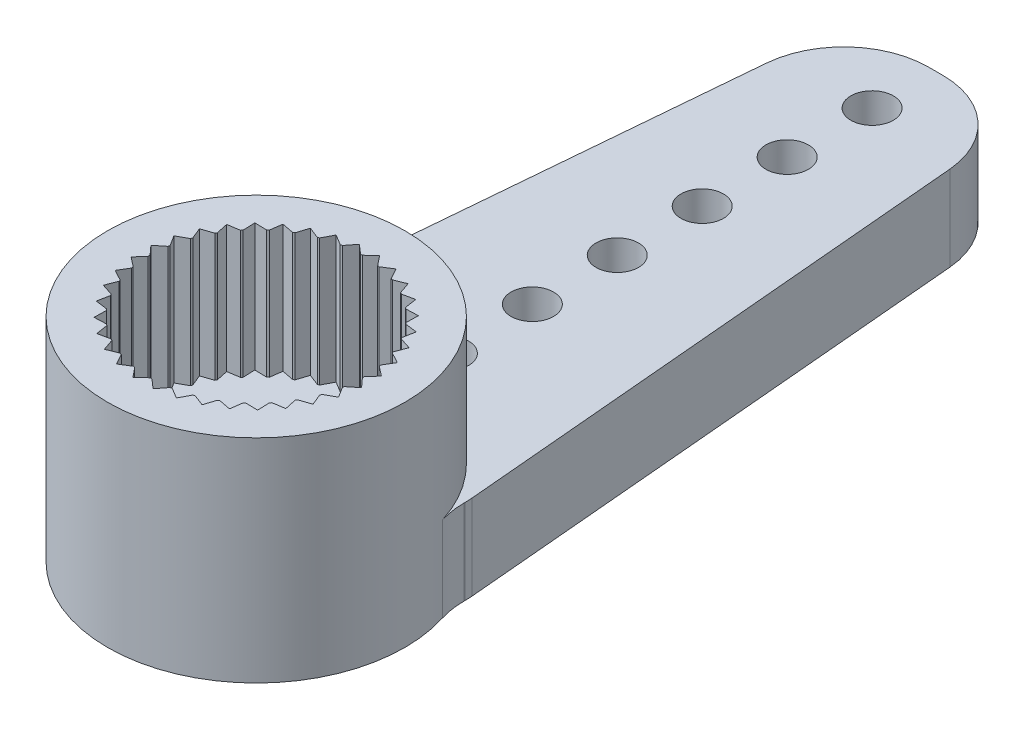
SolidWorks part; units mm, degrees
ref_plane "Front Plane" through (0, 0, 0) normal (0, 0, 1) x (1, 0, 0)
ref_plane "Top Plane" through (0, 0, 0) normal (0, 1, 0) x (1, 0, 0)
ref_plane "Right Plane" through (0, 0, 0) normal (1, 0, 0) x (0, 0, -1)
sketch "Sketch1" plane through (0, 0, 0) normal (0, 1, 0) x (1, 0, 0)
  line L0 (-21.777, 0) -> (33.3507, 0) construction
  line L1 (0, 26.1309) -> (0, -34.4991) construction
  line L2 (-17.4191, 16) -> (29.5794, 16) construction
  line L3 (-18.8664, -16) -> (33.3507, -16) construction
  line L4 (8.5, 26.926) -> (8.5, -27.618) construction
  line L5 (-8.5, 31.6087) -> (-8.5, -32.3009) construction
  line L6 (-24.067, 1.75) -> (35.98, 1.75) construction
  line L7 (-24.067, 0) -> (33.3507, 0) construction
  line L8 (-3.25, 29.5018) -> (-3.25, -36.5148) construction
  line L9 (3.25, 29.5018) -> (3.25, -33.8811) construction
  line L10 (-2, 29.5018) -> (-2, -51.2631) construction
  line L11 (2, 29.5018) -> (2, -51.2631) construction
  line L12 (-3.25, 0) -> (-3.25, 1.75)
  line L13 (-3.25, 1.75) -> (-2, 16)
  line L14 (-2, 16) -> (2, 16)
  line L15 (2, 16) -> (3.25, 1.75)
  line L16 (3.25, 0) -> (3.25, 1.75)
  line L17 (-3.25, 0) -> (3.25, 0)
  dimension "D1" = 16
  dimension "D2" = 16
  dimension "D3" = 8.5
  dimension "D4" = 8.5
  dimension "D5" = 1.75
  dimension "D6" = 0
  dimension "D7" = 3.25
  dimension "D8" = 3.25
  dimension "D9" = 2
  dimension "D10" = 2
extrude "Boss-Extrude1" add sketch "Sketch1" along normal blind 2
fillet "Fillet1" radius 2 2 edges at (-2, 1, -16) (2, 1, -16)
sketch "Sketch2" plane through (0, 2, 0) normal (0, 1, 0) x (1, 0, 0)
  circle A0 centre (0, 0) radius 3.5
extrude "Boss-Extrude2" add sketch "Sketch2" along normal blind 3 and the other way blind 2
sketch "Sketch3" plane through (0, 0, 0) normal (0, -1, 0) x (-1, 0, 0)
  circle A0 centre (0, 0) radius 2.5
extrude "Cut-Extrude1" cut sketch "Sketch3" against normal blind 1
sketch "Sketch4" plane through (0, 1, 0) normal (0, -1, 0) x (-1, 0, 0)
  circle A0 centre (0, 0) radius 1
extrude "Cut-Extrude2" cut sketch "Sketch4" against normal through all
sketch "Sketch5" plane through (0, 5, 0) normal (0, 1, 0) x (1, 0, 0)
  circle A0 centre (0, 0) radius 2.5
extrude "Cut-Extrude3" cut sketch "Sketch5" against normal blind 3
sketch "Sketch6" plane through (0, 5, 0) normal (0, 1, 0) x (1, 0, 0)
  line L0 (-4.6624, 0) -> (4.5112, 0) construction
  line L1 (-5.0093, 0.3942) -> (0, 0) construction
  line L2 (0, 0) -> (6.4397, -0.5068) construction
  line L3 (0, 0) -> (-6.4046, 1.0144) construction
  line L4 (-2.5, 0) -> (-2.6917, 0.2118)
  line L5 (-2.6917, 0.2118) -> (-2.4692, 0.3911)
  line L6 (-2.4692, 0.3911) -> (-2.5, 0)
  circle A0 centre (0, 0) radius 2.7
  circle A1 centre (0, 0) radius 2.5 construction
  dimension "D1" = 4.5
  dimension "D2" = 4.5
extrude "Cut-Extrude4" cut sketch "Sketch6" against normal blind 3 contours L5 L6 L4
sketch "Sketch8" plane through (0, 0, 0) normal (1, 0, 0) x (0, 0, -1)
  line L0 (0, 0) -> (0, 8.8025) construction
pattern_circular "CirPattern1" count 36 over 360 about axis through (0, 0, 0) along (0, 1, 0) of "Cut-Extrude4"
sketch "Sketch9" plane through (0, 0, 0) normal (0, -1, 0) x (-1, 0, 0)
  circle A0 centre (0, 14.5) radius 0.5
extrude "Cut-Extrude5" cut sketch "Sketch9" against normal through all contours A0
sketch "Sketch10" plane through (0, 0, 0) normal (0, -1, 0) x (-1, 0, 0)
  line L0 (0, 13.2867) -> (0, -8.4466) construction
pattern_linear "LPattern1" count 6 spacing 2 along (0, 0, 1) of "Cut-Extrude5"
fillet "Fillet3" radius 2 4 edges at (3.25, 1, -1.75) (3.25, 1, -1.299) (-3.25, 1, -1.75) (-3.25, 1, -1.299)
